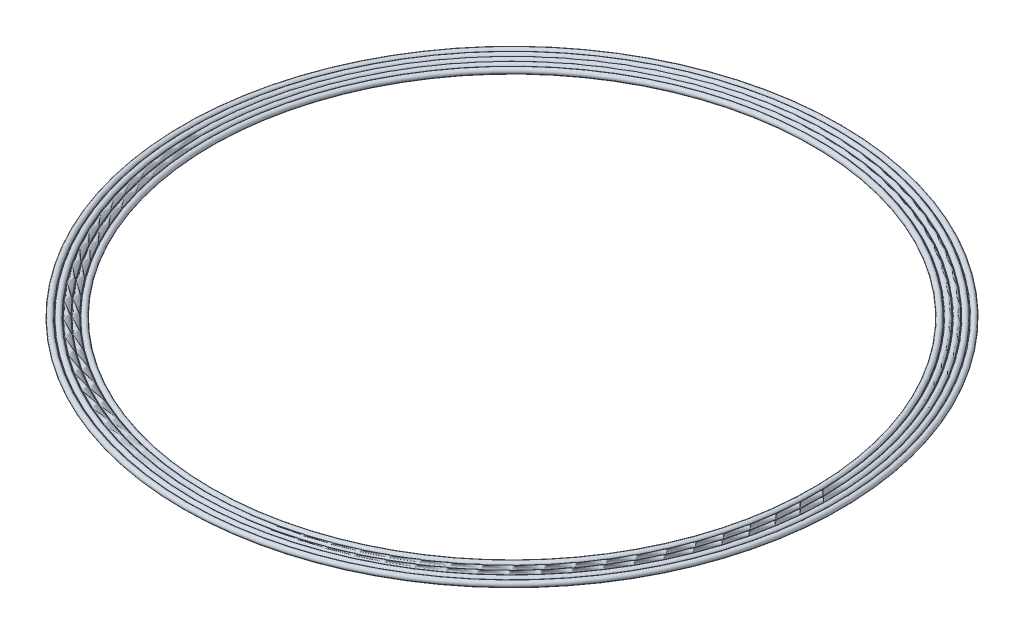
SolidWorks part; units mm, degrees
material "Copper"
ref_plane "Front Plane" through (0, 0, 0) normal (0, 0, 1) x (1, 0, 0)
ref_plane "Top Plane" through (0, 0, 0) normal (0, 1, 0) x (1, 0, 0)
ref_plane "Right Plane" through (0, 0, 0) normal (1, 0, 0) x (0, 0, -1)
sketch "Sketch2" plane through (0, 0, 0) normal (0, 0, 1) x (1, 0, 0)
  line L0 (0, 6.4506) -> (0, -5.0269) construction
  line L1 (0, 0) -> (100, 0) construction
  line L2 (92.5761, 0.2) -> (92.7739, 0.2)
  line L3 (92.5761, -0.2) -> (92.7739, -0.2)
  line L4 (94.4261, -0.2) -> (94.6239, -0.2)
  line L5 (94.4261, 0.2) -> (94.6239, 0.2)
  line L6 (96.2761, 0.2) -> (96.4739, 0.2)
  line L7 (96.2761, -0.2) -> (96.4739, -0.2)
  line L8 (98.1261, -0.2) -> (98.3239, -0.2)
  line L9 (98.1261, 0.2) -> (98.3239, 0.2)
  arc A0 (98.3239, -0.2) -> (98.3239, 0.2) centre (99.15, 0) ccw
  arc A1 (96.4739, -0.2) -> (98.1261, -0.2) centre (97.3, 0) ccw
  arc A2 (94.6239, -0.2) -> (96.2761, -0.2) centre (95.45, 0) ccw
  arc A3 (92.7739, -0.2) -> (94.4261, -0.2) centre (93.6, 0) ccw
  arc A4 (92.5761, 0.2) -> (92.5761, -0.2) centre (91.75, 0) ccw
  arc A5 (94.4261, 0.2) -> (92.7739, 0.2) centre (93.6, 0) ccw
  arc A6 (96.2761, 0.2) -> (94.6239, 0.2) centre (95.45, 0) ccw
  arc A7 (98.1261, 0.2) -> (96.4739, 0.2) centre (97.3, 0) ccw
  point P6 (92.675, -0.2)
  point P15 (90.9, 0)
  dimension "D1" = 1.7
  dimension "D2" = 100
  dimension "D3" = 9.1
  dimension "D4" = 1.85
  dimension "D5" = 1.85
  dimension "D6" = 1.85
  dimension "D7" = 0.2
  dimension "D8" = 0.2
revolve "Revolve1" add sketch "Sketch2" angle 360 about L0
equation "\"D4@Sketch2\"=(\"D3@Sketch2\" -\"D1@Sketch2\")/4"
equation "\"D5@Sketch2\"=\"D4@Sketch2\""
equation "\"D6@Sketch2\"=\"D4@Sketch2\""
